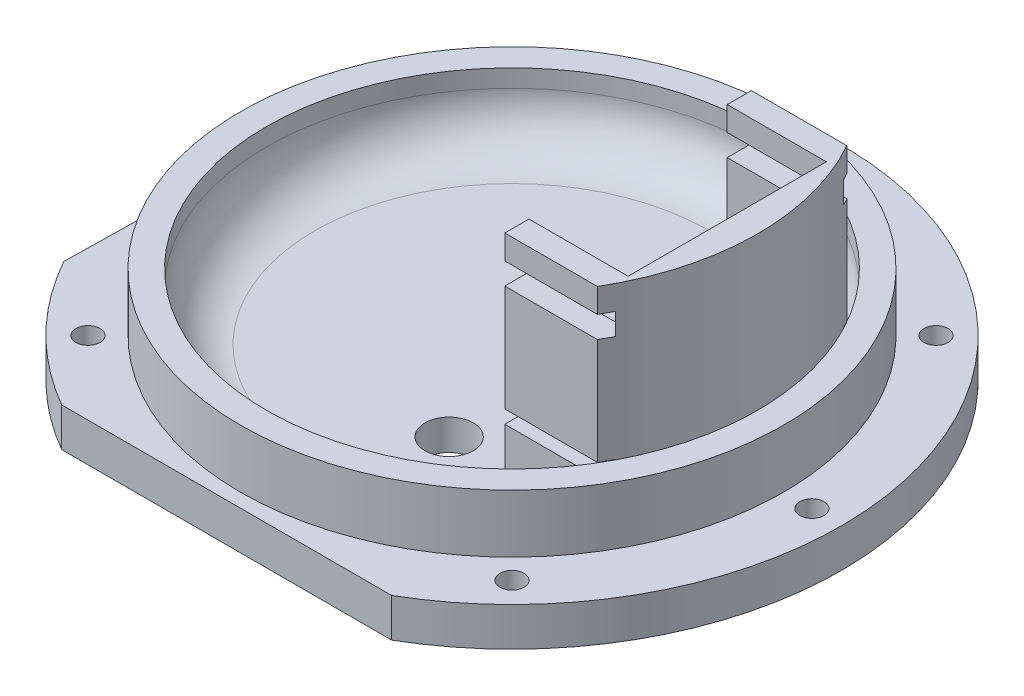
SolidWorks part; units mm, degrees
ref_plane "Front Plane" through (0, 0, 0) normal (0, 0, 1) x (1, 0, 0)
ref_plane "Top Plane" through (0, 0, 0) normal (0, 1, 0) x (1, 0, 0)
ref_plane "Right Plane" through (0, 0, 0) normal (1, 0, 0) x (0, 0, -1)
sketch "Sketch2" plane through (0, 0, 0) normal (0, 1, 0) x (1, 0, 0)
  line L2 (0, 0) -> (-0.3922, 0)
  circle A0 centre (0, 0) radius 50.8
  circle A1 centre (0, 0) radius 57.15
  dimension "D1" = 101.6
  dimension "D2" = 6.35
extrude "Boss-Extrude1" add sketch "Sketch2" along normal blind 203.2 contours A1 A0 region at (-55.5336, 0, 0)
ref_plane "Plane1" through (0, 0, -57.15) normal (0, 0, -1) x (-1, 0, 0)
sketch "Sketch3" plane through (0, 0, -57.15) normal (0, 0, -1) x (-1, 0, 0)
  line L1 (-45, 51.6) -> (45, 51.6)
  line L2 (-45, 51.6) -> (-45, 151.6)
  line L3 (-45, 151.6) -> (45, 151.6)
  line L4 (45, 51.6) -> (45, 151.6)
  line L5 (-45, 101.6) -> (-31.5824, 101.6)
  line L6 (57.15, 203.2) -> (-57.15, 203.2) construction
  line L7 (0, 51.6) -> (0, 42.031)
  line L8 (57.15, 0) -> (57.15, 203.2) construction
  dimension "D1" = 90
  dimension "D2" = 100
  dimension "D3" = 101.6
  dimension "D4" = 57.15
extrude "Cut-Extrude1" cut sketch "Sketch3" against normal blind 58.2 contours L3 L4 L1 L2
sketch "Sketch4" plane through (0, 203.2, 0) normal (0, 1, 0) x (1, 0, 0)
  line L1 (57.0098, -4) -> (38.5933, -4)
  line L2 (57.0098, 4) -> (38.5933, 4)
  line L5 (-57.0098, 4) -> (-38.5933, 4)
  line L6 (-57.0098, -4) -> (-38.5933, -4)
  line L7 (4, 63.2106) -> (4, 31.6501) [skipped]
  line L8 (-4, 63.2106) -> (-4, 31.6501) [skipped]
  line L9 (-4, -63.2106) -> (-4, -31.6501) [skipped]
  line L10 (4, -63.2106) -> (4, -31.6501) [skipped]
  arc A0 (57.0098, 4) -> (-57.0098, 4) centre (0, 0) ccw
  arc A1 (38.5933, 4) -> (-38.5933, 4) centre (0, 0) ccw
  circle A2 centre (0, 0) radius 50.8 construction
  arc A3 (-38.5933, -4) -> (38.5933, -4) centre (0, 0) ccw
  arc A4 (-57.0098, -4) -> (57.0098, -4) centre (0, 0) ccw
  point P28 (0, 0)
  dimension "D1" = 12
  dimension "D3" = 4
extrude "Boss-Extrude2" add sketch "Sketch4" against normal blind 8 contours L2 A1 L5 A0 | L1 A3 L6 A4
ref_plane "Plane2" through (0, 101.6, 0) normal (0, -1, 0) x (-1, 0, 0)
sketch "Sketch5" plane through (0, 0, 0) normal (0, -1, 0) x (1, 0, 0)
  circle A0 centre (0, 0) radius 57.15
extrude "Boss-Extrude3" add sketch "Sketch5" against normal blind 6.35
fillet "Fillet1" radius 10 1 edges at (0, 6.35, -50.8)
fillet "Fillet3" radius 10 1 edges at (0, 203.2, 57.15)
sketch "Sketch8" plane through (0, 51.6, 0) normal (0, 1, 0) x (1, 0, 0)
  line L0 (45, -21) -> (45, 20)
  line L1 (45, 23.572) -> (45, 35.2296) construction
  line L2 (45, 20) -> (24.5, 20)
  line L3 (45, -0.5) -> (50.5035, -0.5)
  line L4 (45, -21) -> (24.5, -21)
  line L5 (50, -26) -> (24.5, -26)
  line L6 (50, -26) -> (50, 25)
  line L7 (50, 25) -> (24.5, 25)
  line L8 (24.5, -26) -> (24.5, -21)
  line L9 (24.5, 25) -> (24.5, 20)
  arc M10 (-45, 23.572) -> (45, 23.572) centre (0, 0) cw
  dimension "D1" = 41
  dimension "D2" = 0
  dimension "D3" = 0
  dimension "D4" = 20.5
  dimension "D6" = 25
  dimension "D5" = 5
extrude "Boss-Extrude4" add sketch "Sketch8" against normal up to surface (45.25 mm away) contours L7 L9 L2 L0 L4 L8 L5 L6 M10 | L9 L2 L0 L4 L8 L5 L6 L7 region at (45.3606, 51.6, -9.75) up to face at (0, 6.35, -40.8)
sketch "Sketch9" plane through (0, 51.6, 0) normal (0, 1, 0) x (1, 0, 0)
  line L0 (50, -8.98) -> (50, 8.98)
  arc A0 (50, -8.98) -> (50, 8.98) centre (0, 0) ccw
extrude "Boss-Extrude5" add sketch "Sketch9" against normal blind 43
sketch "Sketch11" plane through (0, 203.2, 0) normal (0, 1, 0) x (1, 0, 0)
  circle A0 centre (0, 0) radius 72.8342
extrude "Cut-Extrude4" cut sketch "Sketch11" against normal blind 150.35 contours A0
sketch "Sketch13" plane through (0, 52.85, 0) normal (0, 1, 0) x (1, 0, 0)
  circle A0 centre (0, 0) radius 50.8
  circle A1 centre (0, 0) radius 69.7796
extrude "Cut-Extrude6" cut sketch "Sketch13" against normal offset from surface (32.85 mm away) 20 up to face at (0, 0, 57.15)
sketch "Sketch14" plane through (0, 0, 0) normal (0, -1, 0) x (1, 0, 0)
  circle A0 centre (0, 0) radius 57.15
  circle A1 centre (0, 0) radius 75.15
  dimension "D1" = 18
extrude "Boss-Extrude7" add sketch "Sketch14" against normal blind 8
sketch "Sketch15" plane through (24.5, 0, 0) normal (-1, 0, 0) x (0, 0, 1)
  line L0 (-20, 6.35) -> (-20, 51.6) construction
  line L1 (-25, 17.35) -> (-20, 17.35)
  line L2 (-25, 17.35) -> (-25, 20.1)
  line L3 (-25, 20.1) -> (-20, 20.1)
  line L4 (-20, 17.35) -> (-20, 20.1)
  line L5 (-25, 42.1) -> (-20, 42.1)
  line L6 (-25, 42.1) -> (-25, 46.6)
  line L7 (-25, 46.6) -> (-20, 46.6)
  line L8 (-20, 42.1) -> (-20, 46.6)
  line L9 (-25, 6.35) -> (-25, 51.6) construction
  line L10 (-25, 51.6) -> (-20, 51.6) construction
  line L11 (-20, 51.6) -> (21, 51.6)
  line L12 (21, 51.6) -> (0.5, 51.6)
  line L13 (0.5, 51.6) -> (0.5, 60.4276)
  line L14 (21, 42.1) -> (21, 46.6)
  line L15 (26, 46.6) -> (21, 46.6)
  line L16 (26, 42.1) -> (26, 46.6)
  line L17 (26, 42.1) -> (21, 42.1)
  line L18 (21, 17.35) -> (21, 20.1)
  line L19 (26, 20.1) -> (21, 20.1)
  line L20 (26, 17.35) -> (26, 20.1)
  line L21 (26, 17.35) -> (21, 17.35)
  point P12 (-22.5, 46.6)
  line M7 (-25, 51.6) -> (-25, 6.35)
  line M9 (-20, 6.35) -> (-20, 51.6)
  dimension "D1" = 2.75
  dimension "D2" = 4.5
  dimension "D3" = 22
  dimension "D4" = 0
  dimension "D5" = 0
  dimension "D6" = 5
  dimension "D7" = 0
  dimension "D8" = 0
extrude "Cut-Extrude8" cut sketch "Sketch15" against normal up to surface (20.5 mm away) contours L7 L5 M7 M9 | L3 L1 M7 M9 | L21 L20 L19 L18 | L17 L16 L15 L14 region at (24.5, 18.725, -22.5) region at (24.5, 44.35, -22.5) region at (24.5, 44.35, 23.5) region at (24.5, 18.725, 23.5) up to face at (45, 34.9897, -0.0987)
sketch "Sketch16" plane through (0, 0, 0) normal (0, -1, 0) x (1, 0, 0)
  line L0 (54.7379, 16.4283) -> (54.7379, 57.15)
  line L1 (54.7379, 57.15) -> (54.7379, 15.6046)
  line L2 (54.7379, -14.7928) -> (54.7379, -60.9014)
  line L3 (54.7379, -60.9014) -> (96.0311, -32.7311)
  line L4 (96.0311, -32.7311) -> (96.0311, 34.5766)
  line L5 (96.0311, 34.5766) -> (54.7379, 57.15)
  line L6 (0, 0) -> (0, 16.4283)
  line L7 (-96.0311, 34.5766) -> (-54.7379, 57.15)
  line L8 (-96.0311, -32.7311) -> (-96.0311, 34.5766)
  line L9 (-54.7379, -60.9014) -> (-96.0311, -32.7311)
  line L10 (-54.7379, -14.7928) -> (-54.7379, -60.9014)
  line L11 (-54.7379, 57.15) -> (-54.7379, 15.6046)
  line L12 (-54.7379, 16.4283) -> (-54.7379, 57.15)
  circle A0 centre (0, 0) radius 57.15 construction
  circle A1 centre (0, 0) radius 57.15 construction
  arc A2 (61.6129, -5.2936) -> (61.6129, 6.1054) centre (59.7379, 0.4059) ccw
  arc A3 (61.6129, -5.2936) -> (54.7379, -14.7928) centre (64.7379, -14.7928) ccw
  arc A4 (54.7379, 15.6046) -> (61.6129, 6.1054) centre (64.7379, 15.6046) ccw
  arc A5 (-54.7379, 15.6046) -> (-61.6129, 6.1054) centre (-64.7379, 15.6046) cw
  arc A6 (-61.6129, -5.2936) -> (-54.7379, -14.7928) centre (-64.7379, -14.7928) cw
  arc A7 (-61.6129, -5.2936) -> (-61.6129, 6.1054) centre (-59.7379, 0.4059) cw
  circle M3 centre (0, 0) radius 75.15
  dimension "D1" = 12
  dimension "D2" = 5
  dimension "D3" = 10
extrude "Cut-Extrude11" cut sketch "Sketch16" against normal blind 20 contours A6 A7 A5 L11 L10 M3 | L1 A4 A2 A3 L2 L0 M3 region at (55.7877, 0, 33.9595) region at (-55.7877, 0, 33.9595)
sketch "Sketch17" plane through (0, 6.35, 0) normal (0, 1, 0) x (1, 0, 0)
  circle A0 centre (10, -23) radius 5
  dimension "D1" = 10
  dimension "D2" = 23
  dimension "D3" = 10
extrude "Cut-Extrude12" cut sketch "Sketch17" against normal blind 12
sketch "Sketch18" plane through (0, 0, 0) normal (0, -1, 0) x (1, 0, 0)
  circle A0 centre (-59.7379, 0.4059) radius 0.875
  circle A1 centre (-48.0904, 35.4414) radius 0.875
  circle A2 centre (-18.074, 56.9395) radius 0.875
  circle A3 centre (18.846, 56.6887) radius 0.875
  circle A4 centre (48.5675, 34.7847) radius 0.875
  circle A5 centre (59.7379, -0.4059) radius 0.875
  circle A6 centre (48.0904, -35.4414) radius 0.875
  circle A7 centre (18.074, -56.9395) radius 0.875
  circle A8 centre (-18.846, -56.6887) radius 0.875
  circle A9 centre (-48.5675, -34.7847) radius 0.875
  point P23 (0, 0)
  dimension "D1" = 1.75
extrude "Cut-Extrude13" cut sketch "Sketch18" against normal blind 32
sketch "Sketch19" plane through (0, 8, 0) normal (0, 1, 0) x (1, 0, 0)
  circle A0 centre (0, 0) radius 56.65
  arc A1 (-54.7379, -16.4283) -> (54.7379, -16.4283) centre (0, 0) ccw construction
  circle A3 centre (0, 0) radius 61.6614
  dimension "D1" = 0.5
extrude "Cut-Extrude15" cut sketch "Sketch19" along normal blind 57
sketch "Sketch20" plane through (0, 20, 0) normal (0, 1, 0) x (1, 0, 0)
  circle A0 centre (0, 0) radius 56.15
  arc A1 (-54.8318, -14.2371) -> (54.8318, -14.2371) centre (0, 0) ccw construction
  circle A2 centre (0, 0) radius 62.9085
  dimension "D1" = 0.5
extrude "Cut-Extrude18" cut sketch "Sketch20" against normal up to surface (12 mm away) up to face at (0, 8, 38.1223)
sketch "Sketch21" plane through (0, 0, 0) normal (0, -1, 0) x (1, 0, 0)
  circle A0 centre (0, 0) radius 68.15
  circle A1 centre (0, 0) radius 85.1423
  dimension "D1" = 136.3
extrude "Cut-Extrude19" cut sketch "Sketch21" against normal blind 22.3418
sketch "Sketch22" plane through (0, 0, 0) normal (0, -1, 0) x (1, 0, 0)
  line L0 (-54.7379, -40.5979) -> (-54.7379, 40.5979)
  line L1 (-54.7379, 40.5979) -> (-78.9917, 16.344)
  line L2 (-78.9917, 16.344) -> (-75.2406, -31.2343)
  line L3 (-75.2406, -31.2343) -> (-54.7379, -40.5979)
extrude "Cut-Extrude20" cut sketch "Sketch22" against normal blind 22.3418
sketch "Sketch23" plane through (0, 0, 0) normal (0, -1, 0) x (1, 0, 0)
  line L0 (54.7379, -40.5979) -> (54.7379, 40.5979)
  line L1 (54.7379, 40.5979) -> (94.3192, 49.2262)
  line L2 (94.3192, 49.2262) -> (88.5421, -58.9815)
  line L3 (88.5421, -58.9815) -> (54.7379, -40.5979)
extrude "Cut-Extrude21" cut sketch "Sketch23" against normal blind 22.3418
sketch "Sketch24" plane through (0, 8, 0) normal (0, 1, 0) x (1, 0, 0)
  circle A0 centre (0, 0) radius 56.15
  circle A1 centre (0, 0) radius 68.15
extrude "Boss-Extrude8" add sketch "Sketch24" against normal up to surface (8 mm away) up to face at (-48.5675, 0, -35.6597)
sketch "Sketch25" plane through (0, 0, 0) normal (0, -1, 0) x (1, 0, 0)
  line L1 (-59.572, -14.4445) -> (-54.7379, -14.4445)
  line L2 (-59.572, -14.4445) -> (-59.572, 12.5135)
  line L3 (-59.572, 12.5135) -> (-54.7379, 12.5135)
  line L4 (-54.7379, -14.4445) -> (-54.7379, 12.5135)
  line L5 (61.8288, -14.4445) -> (54.7379, -14.4445)
  line L6 (61.8288, -14.4445) -> (61.8288, 12.5135)
  line L7 (61.8288, 12.5135) -> (54.7379, 12.5135)
  line L8 (54.7379, -14.4445) -> (54.7379, 12.5135)
extrude "Boss-Extrude9" add sketch "Sketch25" against normal up to surface (8 mm away) up to face at (0, 8, 0)
sketch "Sketch26" plane through (0, 20, 0) normal (0, 1, 0) x (1, 0, 0)
  circle A0 centre (0, 0) radius 56.15
  circle A1 centre (0, 0) radius 50.8
extrude "Boss-Extrude10" add sketch "Sketch26" against normal up to surface (12 mm away) up to face at (0, 8, 0)
sketch "Sketch27" plane through (0, 0, 0) normal (0, -1, 0) x (1, 0, 0)
  line L0 (-97.4995, 59) -> (123.9007, 59)
  line L1 (-97.4995, 59) -> (3.3533, 131.0659)
  line L2 (3.3533, 131.0659) -> (86.1632, 139.519)
  line L3 (86.1632, 139.519) -> (123.9007, 59)
  dimension "D1" = 59
extrude "Cut-Extrude22" cut sketch "Sketch27" against normal blind 22.3418
sketch "Sketch28" plane through (0, 8, 0) normal (0, 1, 0) x (1, 0, 0)
  line L0 (-59.5839, -33.0784) -> (-58.3983, 35.1292)
  line L1 (-58.3983, 35.1292) -> (-59.5839, -33.0784) construction
  line L2 (-58.3983, 35.1292) -> (-59.5839, -33.0784) construction
  line L3 (-58.3983, 35.1292) -> (-73.1492, 35.3856)
  line L4 (-73.1492, 35.3856) -> (-74.588, -47.3918)
  line L5 (-74.588, -47.3918) -> (-59.5839, -33.0784)
  arc A0 (34.109, -59) -> (-34.109, -59) centre (0, 0) ccw construction
extrude "Cut-Extrude23" cut sketch "Sketch28" against normal blind 23
sketch "Sketch29" plane through (0, 8, 0) normal (0, 1, 0) x (1, 0, 0)
  circle A0 centre (0, 62) radius 2.5
  arc A1 (34.109, -59) -> (-58.3983, 35.1292) centre (0, 0) ccw construction
  circle A2 centre (43.8406, 43.8406) radius 2.5
  circle A3 centre (62, 0) radius 2.5
  circle A4 centre (43.8406, -43.8406) radius 2.5
  circle A5 centre (0, -62) radius 2.5 [skipped]
  circle A6 centre (-43.8406, -43.8406) radius 2.5
  circle A7 centre (-62, 0) radius 2.5 [skipped]
  circle A8 centre (-43.8406, 43.8406) radius 2.5
  point P22 (0, 0)
  dimension "D1" = 5
  dimension "D2" = 62
  dimension "D3" = 8
extrude "Cut-Extrude24" cut sketch "Sketch29" against normal blind 20
